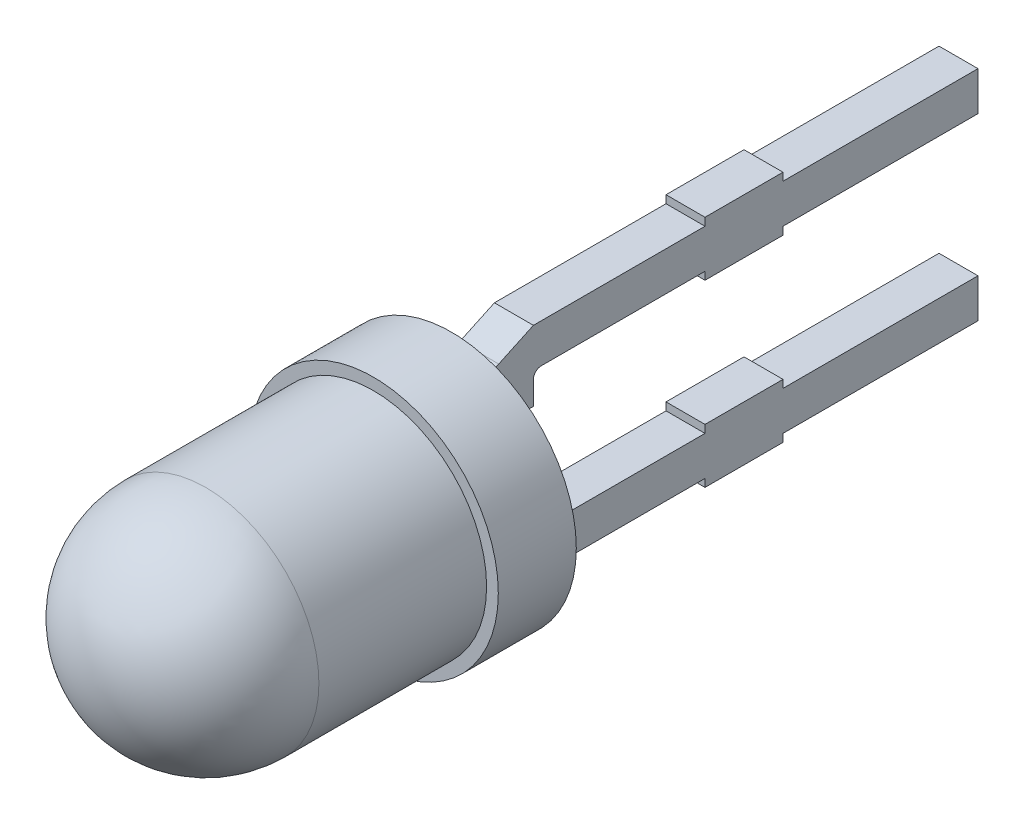
SolidWorks part; units mm, degrees
ref_plane "Front" through (0, 0, 0) normal (0, 0, 1) x (1, 0, 0)
ref_plane "Top" through (0, 0, 0) normal (0, 1, 0) x (1, 0, 0)
ref_plane "Right" through (0, 0, 0) normal (1, 0, 0) x (0, 0, -1)
sketch "Sketch1" plane through (0, 0, 0) normal (1, 0, 0) x (0, 0, -1)
  line L0 (0, 0) -> (76.2974, 0) construction
  line L1 (0, 1.45) -> (2.15, 1.45)
  line L2 (2.15, 1.45) -> (2.15, 1.6)
  line L3 (2.15, 1.6) -> (3.15, 1.6)
  line L4 (3.15, 1.6) -> (3.15, 0)
  line L5 (3.15, 0) -> (-1.45, 0)
  arc A0 (0, 1.45) -> (-1.45, 0) centre (0, 0) ccw
  dimension "D1" = 1.45
  dimension "D2" = 4.6
  dimension "D3" = 1
  dimension "D4" = 1.6
revolve "Revolve1" add sketch "Sketch1" angle 360 about L0
sketch "Sketch2" plane through (0, 0, 0) normal (1, 0, 0) x (0, 0, -1)
  line L0 (3.15, -1.6) -> (3.15, 1.6) construction
  line L1 (3.15, -1.6) -> (3.15, 1.6) construction
  line L2 (3.15, 1.027) -> (3.95, 1.4)
  line L3 (3.95, 1.4) -> (6.15, 1.4)
  line L4 (6.15, 1.4) -> (6.15, 1.5)
  line L5 (6.15, 1.5) -> (7.15, 1.5)
  line L6 (7.15, 1.5) -> (7.15, 1.4)
  line L7 (7.15, 1.4) -> (30.15, 1.4)
  line L8 (30.15, 1.4) -> (30.15, 0.9)
  line L9 (30.15, 0.9) -> (7.15, 0.9)
  line L10 (7.15, 0.9) -> (7.15, 0.8)
  line L11 (7.15, 0.8) -> (6.15, 0.8)
  line L12 (6.15, 0.8) -> (6.15, 0.9)
  line L13 (6.15, 0.9) -> (4.05, 0.9)
  line L14 (3.95, 0.8) -> (3.95, 0.5)
  line L15 (3.95, 0.5) -> (3.15, 0.5)
  line L16 (3.15, 0) -> (7.9733, 0) construction
  line L17 (3.15, 1.027) -> (3.15, 0.5)
  line L18 (3.95, -0.8) -> (3.95, -0.5)
  line L19 (6.15, -0.9) -> (4.05, -0.9)
  line L20 (6.15, -0.8) -> (6.15, -0.9)
  line L21 (7.15, -0.8) -> (6.15, -0.8)
  line L22 (7.15, -0.9) -> (7.15, -0.8)
  line L23 (30.15, -0.9) -> (7.15, -0.9)
  line L24 (30.15, -1.4) -> (30.15, -0.9)
  line L25 (7.15, -1.4) -> (30.15, -1.4)
  line L26 (7.15, -1.5) -> (7.15, -1.4)
  line L27 (6.15, -1.5) -> (7.15, -1.5)
  line L28 (6.15, -1.4) -> (6.15, -1.5)
  line L29 (3.95, -1.4) -> (6.15, -1.4)
  line L30 (3.15, -1.027) -> (3.95, -1.4)
  line L31 (3.15, -1.027) -> (3.15, -0.5)
  line L32 (3.95, -0.5) -> (3.15, -0.5)
  arc A0 (4.05, 0.9) -> (3.95, 0.8) centre (4.05, 0.8) ccw
  arc A1 (4.05, -0.9) -> (3.95, -0.8) centre (4.05, -0.8) cw
  point P19 (3.15, 0)
  dimension "D1" = 0.5
  dimension "D2" = 0.7
  dimension "D3" = 1.4
  dimension "D4" = 0.8
  dimension "D5" = 27
  dimension "D6" = 115
  dimension "D7" = 4
  dimension "D8" = 1
  dimension "D9" = 0.5
  dimension "D10" = 0.1
extrude "Extrude1" add sketch "Sketch2" along normal mid plane 0.5
fillet "Fillet1" radius 0.25 8 edges at (0, -0.5, -3.15) (0, -1.027, -3.15) (-0.25, -0.7635, -3.15) (0, 0.5, -3.15) (-0.25, 0.7635, -3.15) (0, 1.027, -3.15) (0.25, 0.7635, -3.15) (0.25, -0.7635, -3.15)
sketch "Sketch3" plane through (0, 0, 0) normal (1, 0, 0) x (0, 0, -1)
  line L0 (7.15, -1.4) -> (30.15, -1.4) construction
  line L1 (30.15, 1.4) -> (18.15, 1.4)
  line L2 (30.15, 1.4) -> (30.15, -1.4)
  line L3 (30.15, -1.4) -> (18.15, -1.4)
  line L4 (18.15, 1.4) -> (18.15, -1.4)
  dimension "D1" = 15
extrude "Cut-Extrude1" cut sketch "Sketch3" against normal through all both and the other way through all
sketch "Sketch4" plane through (0, 0, 0) normal (1, 0, 0) x (0, 0, -1)
  line L0 (3.15, -1.6) -> (3.15, 1.6) construction
  line L1 (9.65, 2.4154) -> (20.1082, 2.4154)
  line L2 (9.65, 2.4154) -> (9.65, -2.195)
  line L3 (9.65, -2.195) -> (20.1082, -2.195)
  line L4 (20.1082, 2.4154) -> (20.1082, -2.195)
  dimension "D1" = 6.5
extrude "Cut-Extrude2" cut sketch "Sketch4" against normal through all both and the other way through all
